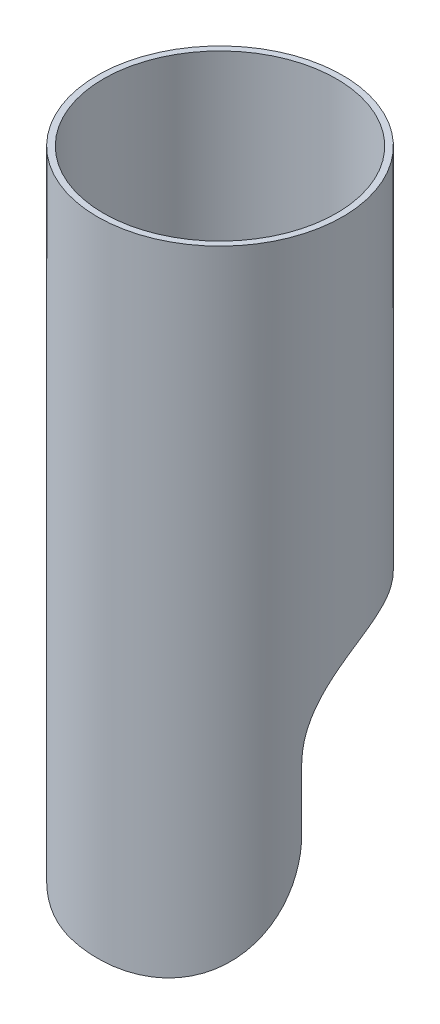
SolidWorks part; units mm, degrees
material "Acrylic (Medium-high impact)"
ref_plane "Front Plane" through (0, 0, 0) normal (0, 0, 1) x (1, 0, 0)
ref_plane "Top Plane" through (0, 0, 0) normal (0, 1, 0) x (1, 0, 0)
ref_plane "Right Plane" through (0, 0, 0) normal (1, 0, 0) x (0, 0, -1)
sketch "Sketch1" plane through (0, 0, 0) normal (0, 1, 0) x (1, 0, 0)
  circle A0 centre (0, 0) radius 19.05
  circle A1 centre (0, 0) radius 20.05
  dimension "D1" = 38.1
  dimension "D2" = 1
extrude "Boss-Extrude1" add sketch "Sketch1" along normal blind 60
sketch "Sketch2" plane through (0, 0, 0) normal (0, -1, 0) x (1, 0, 0)
  line L0 (19.325, 5.8809) -> (17.9708, 5.3492) construction
  line L1 (19.325, 5.8809) -> (17.9708, 5.3492)
  line L2 (0, 0) -> (-2.0952, 18.5822) construction
  line L3 (-20.1493, 1.4299) -> (-18.7107, 1.2132)
  circle A0 centre (0, 0) radius 20.05 construction
  circle A1 centre (0, 0) radius 20.05
  arc A2 (18.3446, 3.6283) -> (-18.692, -0.5478) centre (0, 0) ccw construction
  arc A3 (18.3446, 3.6283) -> (-18.692, -0.5478) centre (0, 0) ccw
  circle A4 centre (0, 0) radius 19.05 construction
  circle A5 centre (0, 0) radius 19.05
  circle M1 centre (0, 0) radius 20.05
  circle M2 centre (0, 0) radius 19.05
extrude "Boss-Extrude2" add sketch "Sketch2" along normal blind 45 contours L3 L1 M1 M2 region at (18.5592, 0, 6.0471)
fillet "Fillet1" radius 20 2 edges at (18.718, -45, 5.6426) (-19.5045, -45, 1.3328) first distance on face at (-1.2919, -45, 11.4573) first distance on face at (-19.5045, -22.5, 1.3328)
fillet "Fillet2" radius 15 2 edges at (-19.5045, 0, 1.3328) (18.718, 0, 5.6426) first distance on face at (0.8986, 0, -7.9696) first distance on face at (18.8347, -12.5, 5.6884)
